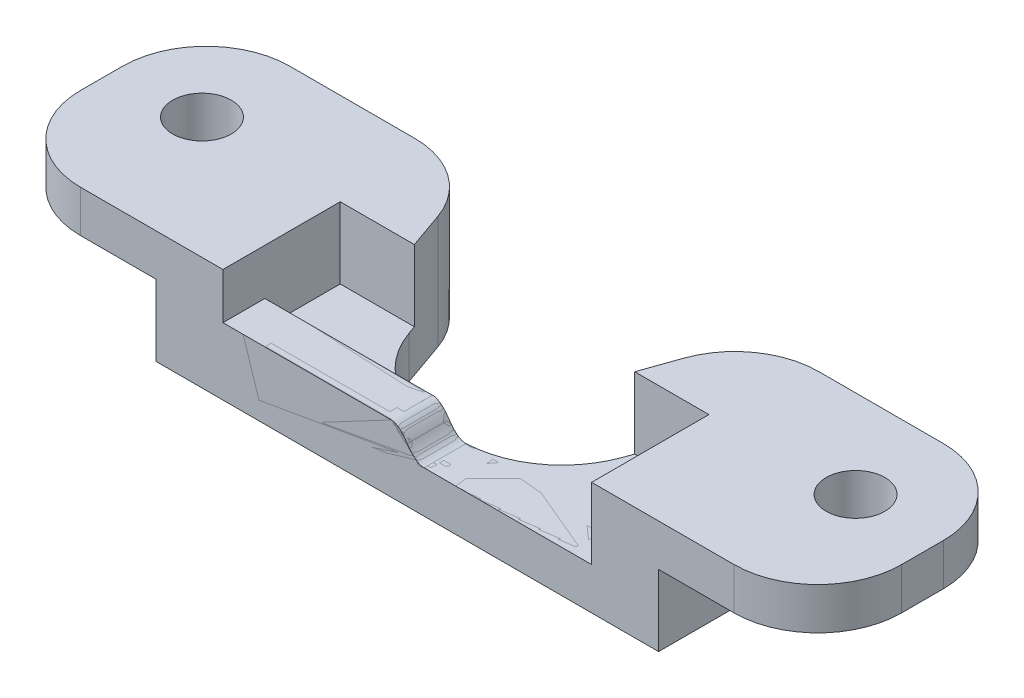
SolidWorks part; units mm, degrees
ref_plane "前视基准面" through (0, 0, 0) normal (0, 0, 1) x (1, 0, 0)
ref_plane "上视基准面" through (0, 0, 0) normal (0, 1, 0) x (1, 0, 0)
ref_plane "右视基准面" through (0, 0, 0) normal (1, 0, 0) x (0, 0, -1)
ref_axis "基准轴1" through (0, 0, -88.99) along (0, 0, 1)
sketch "草图1" plane through (0, 0, 0) normal (0, 0, 1) x (1, 0, 0)
  line L0 (0, 0) -> (0, 3)
  line L1 (0, 3) -> (15, 3)
  line L2 (19, 0) -> (34, 0)
  line L3 (0, 0) -> (0, -5)
  line L4 (0, -5) -> (34, -5)
  line L5 (34, 0) -> (34, -5)
  spline S0 degree 3 poles (15, 3) (15.084, 3) (15.2542, 2.9837) (15.5078, 2.9112) (15.7601, 2.7912) (16.0113, 2.6243) (16.2617, 2.4109) (16.5114, 2.1508) (16.7621, 1.845) (17, 1.5) (17.2379, 1.155) (17.4886, 0.8492) (17.7383, 0.5891) (17.9887, 0.3757) (18.2399, 0.2088) (18.4922, 0.0888) (18.7458, 0.0163) (18.916, 0) (19, 0) knots 0 0 0 0 0.048331 0.098318 0.151463 0.20902 0.27198 0.341104 0.416966 0.5 0.583034 0.658896 0.72802 0.79098 0.848537 0.901682 0.951669 1 1 1 1
extrude "凸台-拉伸1" add sketch "草图1" along normal blind 5
sketch "草图2" plane through (0, 0, 0) normal (0, 1, 0) x (1, 0, 0)
  line L0 (17, 15.9843) -> (17, 0) construction
  line L1 (-13, 20) -> (0, 20)
  line L2 (-13, 20) -> (-13, -5)
  line L3 (-13, -5) -> (47, -5)
  line L4 (47, 20) -> (47, -5)
  line L5 (0, 0) -> (34, 0) construction
  line L6 (0, 0) -> (34, 0) construction
  line L7 (15, -5) -> (0, -5) construction
  line L8 (0, 20) -> (7, 0)
  line L9 (7, 0) -> (27, 0)
  line L10 (34, 20) -> (47, 20)
  line L11 (27, 0) -> (34, 20)
  line L12 (0, 0) -> (34, 0) construction
  line L13 (0, -5) -> (0, 0) construction
  dimension "D1" = 10
  dimension "D5" = 30
  dimension "D4" = 25
extrude "凸台-拉伸2" add sketch "草图2" against normal up to surface (5 mm away) up to face at (17, -5, 2.5)
sketch "草图3" plane through (0, 0, 0) normal (0, 1, 0) x (1, 0, 0)
  line L0 (-13, -5) -> (0, -5) construction
  line L1 (-32, 20) -> (0, 20)
  line L2 (-32, 20) -> (-32, -5)
  line L3 (-32, -5) -> (-5, -5)
  line L4 (-5, -5) -> (-5, 9)
  line L5 (0, 20) -> (-13, 20) construction
  line L6 (30.15, 9) -> (34, 20)
  line L7 (39, 9) -> (30.15, 9)
  line L8 (0, 0) -> (34, 0) construction
  line L9 (0, 0) -> (34, 0) construction
  line L10 (17, 0) -> (17, 25.7819) construction
  line L11 (39, -5) -> (39, 9)
  line L12 (66, -5) -> (39, -5)
  line L13 (66, 20) -> (66, -5)
  line L14 (66, 20) -> (34, 20)
  line L15 (-5, 9) -> (3.85, 9)
  line L16 (7, 0) -> (0, 20) construction
  line L17 (3.85, 9) -> (0, 20)
  circle A0 centre (-22, 9.5) radius 3.5
  circle A1 centre (56, 9.5) radius 3.5
  dimension "D3" = 14.5
  dimension "D5" = 7
  dimension "D1" = 22
  dimension "D2" = 27
  dimension "D4" = 39
  dimension "D6" = 9
extrude "凸台-拉伸3" add sketch "草图3" along normal blind 8.5
sketch "草图4" plane through (0, 0, 5) normal (0, 0, 1) x (1, 0, 0)
  line L1 (-13, 0) -> (-32, 0)
  line L2 (-13, 0) -> (-13, 3.5)
  line L3 (-13, 3.5) -> (-32, 3.5)
  line L4 (-32, 0) -> (-32, 3.5)
  line L5 (66, 8.5) -> (66, 0) construction
  line L6 (47, 0) -> (66, 0)
  line L7 (47, 0) -> (47, 3.5)
  line L8 (47, 3.5) -> (66, 3.5)
  line L9 (66, 0) -> (66, 3.5)
  line L10 (-32, 8.5) -> (-32, 0) construction
  dimension "D1" = 3.5
extrude "切除-拉伸1" cut sketch "草图4" against normal up to next
fillet "圆角5" radius 10 6 edges at (-32, 6, -20) (-32, 6, 5) (66, 6, 5) (66, 6, -20) (0, 1.75, -20) (34, 1.75, -20)
fillet "圆角6" radius 12 2 edges at (7, -2.5, 0) (27, -2.5, 0)
sketch "草图5" plane through (0, 0, 0) normal (-1, 0, 0) x (0, 0, 1)
  line L4 (0, 3) -> (0, 0)
  line L5 (0, 0) -> (5, 0)
  line L6 (5, 0) -> (5, 3)
  line L7 (5, 3) -> (0, 3)
  line L8 (0, 3) -> (0, 0)
  line L9 (0, 0) -> (5, 0)
  line L10 (5, 0) -> (5, 3)
  line L11 (5, 3) -> (0, 3)
  dimension "D1" = 0
extrude "凸台-拉伸4" add sketch "草图5" along normal up to next
ref_axis "基准轴2" through (-22, 8.5, -9.5) along (0, -1, 0)
ref_plane "基准面1" through (0, 0, -9.5) normal (0, 0, -1) x (0, -1, 0)
sketch "草图7" plane through (0, 0, 0) normal (0, 0, 1) x (1, 0, 0)
  line L0 (0, -5) -> (34, -5) construction
  line L1 (0, 3) -> (15, 3) construction
  line L2 (19, 0) -> (34, 0) construction
  line L3 (0, -5) -> (34, -5) construction
  line L4 (0, 3) -> (15, 3) construction
  line L5 (19, 0) -> (34, 0) construction
  line L8 (34, 0) -> (37, 0) construction
  line L9 (37, -5) -> (34, -5) construction
  line L10 (0, -5) -> (-3, -5) construction
  line L11 (-3, 3) -> (0, 3) construction
  line L12 (34, 0) -> (34, -5) construction
  line L13 (0, 0) -> (0, -5) construction
  arc A0 (37, 0) -> (37, -5) centre (37, -2.5) cw construction
  arc A1 (-3, -5) -> (-3, 3) centre (-3, -1) cw construction
  spline S0 degree 3 poles (2395.6211, -1817.7965) (-32.0714, -130.5688) (4.3227, 6.1083) (15.5078, 2.9112) (15.7601, 2.7912) (16.0113, 2.6243) (16.2617, 2.4109) (16.5114, 2.1508) (16.7621, 1.845) (17, 1.5) (17.2379, 1.155) (17.4886, 0.8492) (17.7383, 0.5891) (17.9887, 0.3757) (18.2399, 0.2088) (18.4922, 0.0888) (29.6772, -3.1083) (66.0709, 133.5668) (-2361.5695, 1820.7607) knots -6.528662 -6.528662 -6.528662 -6.528662 0.048331 0.098318 0.151463 0.20902 0.27198 0.341104 0.416966 0.5 0.583034 0.658896 0.72802 0.79098 0.848537 0.901682 0.951669 7.528615 7.528615 7.528615 7.528615 only from (15, 3) to (19, 0) construction
  spline S1 degree 3 poles (15, 3) (15.084, 3) (15.2542, 2.9837) (15.5078, 2.9112) (15.7601, 2.7912) (16.0113, 2.6243) (16.2617, 2.4109) (16.5114, 2.1508) (16.7621, 1.845) (17, 1.5) (17.2379, 1.155) (17.4886, 0.8492) (17.7383, 0.5891) (17.9887, 0.3757) (18.2399, 0.2088) (18.4922, 0.0888) (18.7458, 0.0163) (18.916, 0) (19, 0) knots 0 0 0 0 0.048331 0.098318 0.151463 0.20902 0.27198 0.341104 0.416966 0.5 0.583034 0.658896 0.72802 0.79098 0.848537 0.901682 0.951669 1 1 1 1 construction
  spline S2 degree 3 poles (0, -5) (11.3333, -5) (22.6667, -5) (34, -5) (34.75, -5) (35.5, -5) (36.25, -5) (36.3333, -5) (36.5, -5) (36.75, -5) (36.9167, -5) (37, -5) (37.0852, -5) (37.2555, -5) (37.5114, -4.9516) (37.6764, -4.9083) (37.7575, -4.8825) (40.585, -3.9835) (40.585, -1.0165) (37.7575, -0.1175) (37.6764, -0.0917) (37.5114, -0.0484) (37.2555, 0) (37.0852, 0) (37, 0) (36.9167, 0) (36.75, 0) (36.5, 0) (36.3333, 0) (36.25, 0) (35.5, 0) (34.75, 0) (34, 0) (29.4239, 0) (24.8478, 0) (20.2717, 0) (20.1292, 0) (19.844, 0) (19.4163, 0) (19.1312, 0) (18.9887, 0) (18.8994, 0) (18.721, 0) (18.4435, 0.0804) (18.2928, 0.1758) (18.2174, 0.2235) (18.1725, 0.2519) (18.0828, 0.3087) (17.9563, 0.4065) (17.8746, 0.4743) (17.8347, 0.5092) (17.806, 0.5343) (17.6891, 0.6404) (17.4886, 0.8492) (17.2379, 1.155) (17, 1.5) (16.7621, 1.845) (16.5114, 2.1508) (16.3109, 2.3596) (16.194, 2.4657) (16.1653, 2.4908) (16.1254, 2.5257) (16.0437, 2.5935) (15.9172, 2.6913) (15.8275, 2.7481) (15.7826, 2.7765) (15.7072, 2.8242) (15.5565, 2.9196) (15.279, 3) (15.1006, 3) (15.0113, 3) (14.8688, 3) (14.5837, 3) (14.156, 3) (13.8708, 3) (13.7283, 3) (9.1522, 3) (4.5761, 3) (0, 3) (-0.75, 3) (-1.5, 3) (-2.25, 3) (-2.3333, 3) (-2.5, 3) (-2.75, 3) (-2.9167, 3) (-3, 3) (-3.0854, 3) (-3.2561, 3) (-3.5124, 2.9698) (-3.6811, 2.9425) (-3.7649, 2.9262) (-9.3401, 1.84) (-9.3401, -3.84) (-3.7649, -4.9262) (-3.6811, -4.9425) (-3.5124, -4.9698) (-3.2561, -5) (-3.0854, -5) (-3, -5) (-2.9167, -5) (-2.75, -5) (-2.5, -5) (-2.3333, -5) (-2.25, -5) (-1.5, -5) (-0.75, -5) (0, -5) (11.3333, -5) (22.6667, -5) knots -0.023227 0 0 0 0.350985 0.350985 0.350985 0.374212 0.374212 0.374212 0.376793 0.379373 0.381954 0.381954 0.381954 0.384592 0.38723 0.389868 0.389868 0.389868 0.439057 0.439057 0.439057 0.441694 0.444332 0.44697 0.44697 0.44697 0.449551 0.452132 0.454712 0.454712 0.454712 0.477939 0.477939 0.477939 0.619657 0.619657 0.619657 0.624072 0.628488 0.632903 0.632903 0.632903 0.635666 0.638429 0.641193 0.641193 0.641193 0.642836 0.644479 0.646123 0.646123 0.646123 0.647302 0.651011 0.655082 0.659537 0.663993 0.668064 0.671773 0.672952 0.672952 0.672952 0.674595 0.676239 0.677882 0.677882 0.677882 0.680645 0.683409 0.686172 0.686172 0.686172 0.690587 0.695002 0.699417 0.699417 0.699417 0.841135 0.841135 0.841135 0.864362 0.864362 0.864362 0.866943 0.869524 0.872105 0.872105 0.872105 0.874749 0.877393 0.880037 0.880037 0.880037 0.961098 0.961098 0.961098 0.963742 0.966387 0.969031 0.969031 0.969031 0.971612 0.974192 0.976773 0.976773 0.976773 1 1 1 1.350985 1.350985 1.350985 weights 1 1 1 1 1 1 1 1 1 1 1 1 1 1 1 1 1 0.535341 0.535341 1 1 1 1 1 1 1 1 1 1 1 1 1 1 1 1 1 1 1 1 1 1 1 1 1 1 1 1 1 1 1 1 1 1 1 1 1 1 1 1 1 1 1 1 1 1 1 1 1 1 1 1 1 1 1 1 1 1 1 1 1 1 1 1 1 1 1 1 1 1 1 1 1 0.460815 0.460815 1 1 1 1 1 1 1 1 1 1 1 1 1 1 1 1 only from (0, -5) to (0, -5)
  dimension "D1" = 3
  dimension "D2" = 3
extrude "凸台-拉伸5" add sketch "草图7" along normal blind 5 separate body
hole_wizard "大小mm Transitional 暗销孔0" positions "草图8" profile "草图9" hole size "Ø2.0" standard "GB"
sketch "草图8" plane through (0, -5, 0) normal (0, -1, 0) x (-1, 0, 0)
  line L0 (0, 0) -> (16.2813, 0) construction
  line L2 (0, 0) -> (0, 18.1041) construction
  line L4 (-17, 52.4609) -> (-17, -37.6029) construction
  line L6 (13, -5) -> (13, 20) construction
  line L7 (-47, 20) -> (-47, -5) construction
  point P0 (-44.5, 7)
  point P3 (-44.5, 12)
  point P6 (10.5, 7)
  point P9 (10.5, 12)
  point P33 (0, 0)
  point P34 (0, 0)
  point P35 (0, 0)
  point P36 (0, 0)
  dimension "D1" = 7
  dimension "D2" = 10.5
  dimension "D3" = 5
sketch "草图9" plane through (44.5, -5, -7) normal (1, 0, 0) x (0, 0, -1)
  line L0 (0, 0) -> (0, 5.6009)
  line L1 (0, 5.6009) -> (1, 5)
  line L2 (1, 5) -> (1, 0)
  line L5 (1, 0) -> (0, 0)
  line L10 (0, 5.6009) -> (-1, 5) construction
  line L11 (0, -6.35) -> (0, 107.95) construction
  dimension "孔直径" = 2
  dimension "孔深度" = 5
  dimension "导头角度" = 118
